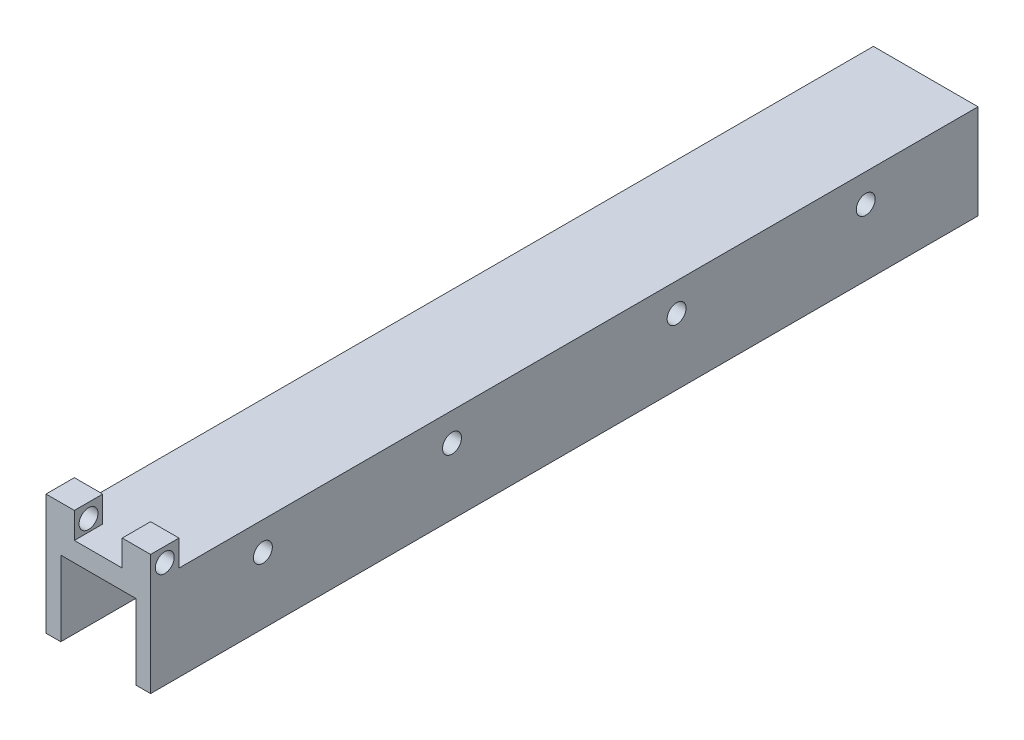
SolidWorks part; units mm, degrees
ref_plane "Front Plane" through (0, 0, 0) normal (0, 0, 1) x (1, 0, 0)
ref_plane "Top Plane" through (0, 0, 0) normal (0, 1, 0) x (1, 0, 0)
ref_plane "Right Plane" through (0, 0, 0) normal (1, 0, 0) x (0, 0, -1)
sketch "Sketch2" plane through (0, 0, 0) normal (0, 0, 1) x (1, 0, 0)
  line L0 (319.8414, 0) -> (-319.8414, 0) construction
  line L2 (0, 0) -> (0, 20.32)
  line L3 (0, 20.32) -> (22.479, 20.32)
  line L4 (22.479, 0) -> (22.479, 20.32)
  line L44 (19.304, 16.129) -> (19.304, 0)
  line L47 (3.175, 0) -> (3.175, 16.129)
  line L48 (3.175, 16.129) -> (19.304, 16.129)
  line L49 (0, 0) -> (3.175, 0)
  line L50 (19.304, 0) -> (22.479, 0)
  dimension "D1" = 20.32
  dimension "D2" = 22.479
  dimension "D3" = 3.175
  dimension "D4" = 16.129
  dimension "D5" = 3.175
  dimension "D7" = 16.129
extrude "Boss-Extrude2" add sketch "Sketch2" against normal blind 177.8
sketch "Sketch19" plane through (0, 0, 0) normal (1, 0, 0) x (0, 0, -1)
  line L0 (0, 265.0009) -> (0, -265.0009) construction
  line L1 (319.8414, 0) -> (-319.8414, 0) construction
  line L3 (0, 0) -> (88.9, 0) construction
  line L4 (177.8, 0) -> (0, 0) construction
  line L5 (88.9, 0) -> (88.9, 20.32) construction
  line L6 (177.8, 20.32) -> (0, 20.32) construction
  line L7 (177.8, 0) -> (177.8, 20.32) construction
  circle A0 centre (24.13, 14.224) radius 2.032
  circle A1 centre (64.77, 14.224) radius 2.032
  circle A2 centre (113.03, 14.224) radius 2.032
  circle A3 centre (153.67, 14.224) radius 2.032
  dimension "D2" = 4.064
  dimension "D5" = 4.064
  dimension "D9" = 24.13
  dimension "D1" = 24.13
  dimension "D3" = 14.224
  dimension "D4" = 40.64
  dimension "D6" = 14.224
  dimension "D7" = 24.13
  dimension "D8" = 88.9
  dimension "D10" = 40.64
  dimension "D11" = 24.13
extrude "Cut-Extrude3" cut sketch "Sketch19" along normal through all
sketch "Sketch20" plane through (22.479, 0, 0) normal (1, 0, 0) x (0, 0, -1)
sketch "Sketch21" plane through (0, 20.32, 0) normal (0, 1, 0) x (1, 0, 0)
  line L0 (11.2395, 0) -> (11.2395, 177.8) construction
  line L1 (0, 0) -> (22.479, 0) construction
  line L2 (0, 0) -> (6.096, 0)
  line L3 (0, 0) -> (0, 6.096)
  line L4 (0, 6.096) -> (6.096, 6.096)
  line L5 (6.096, 0) -> (6.096, 6.096)
  line L6 (22.479, 177.8) -> (0, 177.8) construction
  line L7 (0, 0) -> (6.096, 0) construction
  line L8 (6.096, 0) -> (6.096, 6.5548) construction
  line L10 (16.383, 0) -> (16.383, 6.5548) construction
  line L11 (22.479, 0) -> (16.383, 0)
  line L12 (22.479, 0) -> (22.479, 6.096)
  line L13 (22.479, 6.096) -> (16.383, 6.096)
  line L14 (16.383, 0) -> (16.383, 6.096)
  dimension "D1" = 6.096
  dimension "D2" = 6.096
  dimension "D3" = 6.096
  dimension "D4" = 10.287
  dimension "D5" = 6.096
  dimension "D6" = 6.096
  dimension "D7" = 6.096
extrude "Boss-Extrude4" add sketch "Sketch21" along normal blind 5.588
sketch "Sketch22" plane through (16.383, 0, 0) normal (-1, 0, 0) x (0, 0, 1)
  line L0 (0, 25.908) -> (-6.096, 25.908) construction
  line L1 (0, -265.0009) -> (0, 265.0009) construction
  line L2 (0, 25.908) -> (0, 0) construction
  line L3 (-177.8, 20.32) -> (-6.096, 20.32) construction
  line L4 (-177.8, 0) -> (0, 0) construction
  circle A0 centre (-3.048, 22.86) radius 2.032
  point P4 (-3.048, 25.908)
  point P13 (0, 0)
  point P14 (0, 0)
  dimension "D1" = 4.064
  dimension "D2" = 3.048
  dimension "D3" = 3.048
extrude "Cut-Extrude4" cut sketch "Sketch22" against normal through all both and the other way through all
